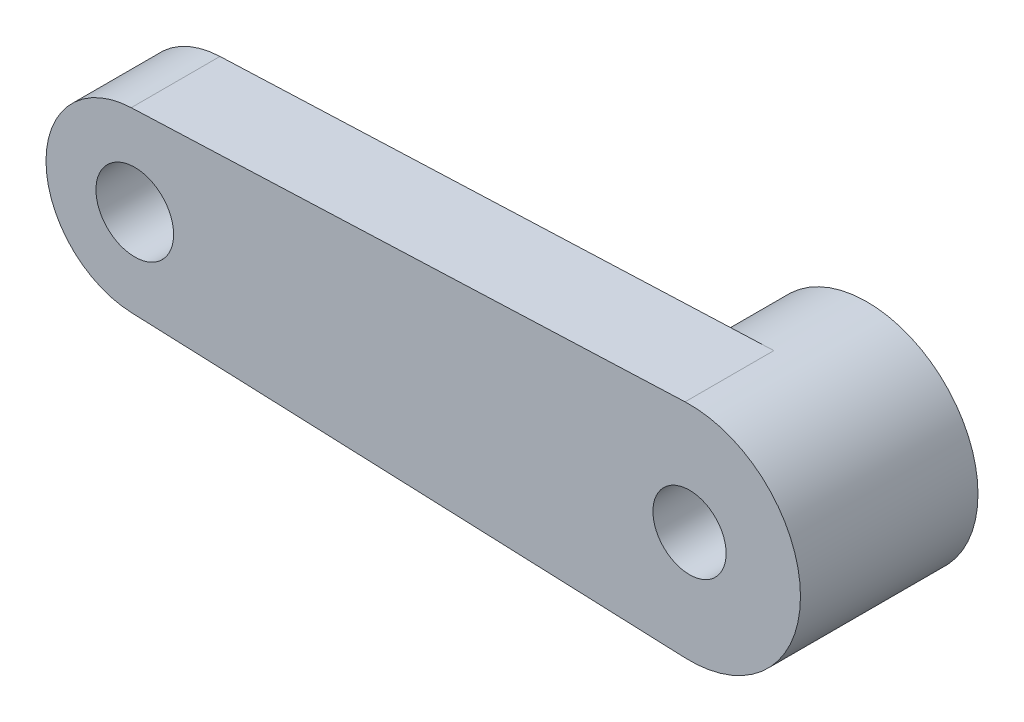
SolidWorks part; units mm, degrees
ref_plane "Front Plane" through (0, 0, 0) normal (0, 0, 1) x (1, 0, 0)
ref_plane "Top Plane" through (0, 0, 0) normal (0, 1, 0) x (1, 0, 0)
ref_plane "Right Plane" through (0, 0, 0) normal (1, 0, 0) x (0, 0, -1)
sketch "Sketch1" plane through (0, 0, 0) normal (0, 0, 1) x (1, 0, 0)
  line L96 (0.2308, 2.8251) -> (0.1696, 2.7453)
  line L97 (0.1696, 2.7453) -> (0.1212, 2.8292)
  line L98 (-0.1379, 2.8447) -> (-0.1902, 2.7542)
  line L99 (-0.1902, 2.7542) -> (-0.2514, 2.834)
  line L100 (-0.509, 2.8001) -> (-0.5474, 2.7072)
  line L101 (-0.5474, 2.7072) -> (-0.6186, 2.7783)
  line L102 (-0.8695, 2.7111) -> (-0.8955, 2.6139)
  line L103 (-0.8955, 2.6139) -> (-0.9753, 2.6752)
  line L104 (-1.2153, 2.5757) -> (-1.2285, 2.476)
  line L105 (-1.2285, 2.476) -> (-1.3156, 2.5263)
  line L106 (-1.5406, 2.3964) -> (-1.5406, 2.2958)
  line L107 (-1.5406, 2.2958) -> (-1.6335, 2.3343)
  line L108 (-1.8396, 2.1762) -> (-1.8265, 2.0765)
  line L109 (-1.8265, 2.0765) -> (-1.9236, 2.1025)
  line L110 (-2.1073, 1.9188) -> (-2.0813, 1.8216)
  line L111 (-2.0813, 1.8216) -> (-2.181, 1.8348)
  line L112 (-2.3391, 1.6287) -> (-2.3007, 1.5357)
  line L113 (-2.3007, 1.5357) -> (-2.4012, 1.5357)
  line L114 (-2.5311, 1.3107) -> (-2.4809, 1.2237)
  line L115 (-2.4809, 1.2237) -> (-2.5806, 1.2105)
  line L116 (-2.68, 0.9705) -> (-2.6188, 0.8907)
  line L117 (-2.6188, 0.8907) -> (-2.7159, 0.8647)
  line L118 (-2.7831, 0.6137) -> (-2.712, 0.5426)
  line L119 (-2.712, 0.5426) -> (-2.8049, 0.5041)
  line L120 (-2.8388, 0.2466) -> (-2.7591, 0.1853)
  line L121 (-2.7591, 0.1853) -> (-2.8462, 0.1351)
  line L122 (-2.8462, -0.1248) -> (-2.7591, -0.175)
  line L123 (-2.7591, -0.175) -> (-2.8388, -0.2363)
  line L124 (-2.8049, -0.4938) -> (-2.712, -0.5323)
  line L125 (-2.712, -0.5323) -> (-2.7831, -0.6034)
  line L126 (-2.7159, -0.8544) -> (-2.6188, -0.8804)
  line L127 (-2.6188, -0.8804) -> (-2.68, -0.9602)
  line L128 (-2.5806, -1.2002) -> (-2.4809, -1.2134)
  line L129 (-2.4809, -1.2134) -> (-2.5311, -1.3004)
  line L130 (-2.4012, -1.5254) -> (-2.3007, -1.5254)
  line L131 (-2.3007, -1.5254) -> (-2.3391, -1.6184)
  line L132 (-2.181, -1.8245) -> (-2.0813, -1.8113)
  line L133 (-2.0813, -1.8113) -> (-2.1073, -1.9085)
  line L134 (-1.9236, -2.0922) -> (-1.8265, -2.0662)
  line L135 (-1.8265, -2.0662) -> (-1.8396, -2.1659)
  line L136 (-1.6335, -2.324) -> (-1.5406, -2.2855)
  line L137 (-1.5406, -2.2855) -> (-1.5406, -2.3861)
  line L138 (-1.3156, -2.516) -> (-1.2285, -2.4657)
  line L139 (-1.2285, -2.4657) -> (-1.2153, -2.5654)
  line L140 (-0.9753, -2.6649) -> (-0.8955, -2.6036)
  line L141 (-0.8955, -2.6036) -> (-0.8695, -2.7008)
  line L142 (-0.6186, -2.768) -> (-0.5474, -2.6969)
  line L143 (-0.5474, -2.6969) -> (-0.509, -2.7898)
  line L144 (-0.2514, -2.8237) -> (-0.1902, -2.7439)
  line L145 (-0.1902, -2.7439) -> (-0.1399, -2.831)
  line L146 (0.1199, -2.831) -> (0.1702, -2.7439)
  line L147 (0.1702, -2.7439) -> (0.2314, -2.8237)
  line L148 (0.489, -2.7898) -> (0.5275, -2.6969)
  line L149 (0.5275, -2.6969) -> (0.5986, -2.768)
  line L150 (0.8496, -2.7008) -> (0.8756, -2.6036)
  line L151 (0.8756, -2.6036) -> (0.9554, -2.6649)
  line L152 (1.1954, -2.5654) -> (1.2085, -2.4657)
  line L153 (1.2085, -2.4657) -> (1.2956, -2.516)
  line L154 (1.5206, -2.3861) -> (1.5206, -2.2855)
  line L155 (1.5206, -2.2855) -> (1.6135, -2.324)
  line L156 (1.8197, -2.1659) -> (1.8065, -2.0662)
  line L157 (1.8065, -2.0662) -> (1.9037, -2.0922)
  line L158 (2.0874, -1.9085) -> (2.0613, -1.8113)
  line L159 (2.0613, -1.8113) -> (2.161, -1.8245)
  line L160 (2.3192, -1.6184) -> (2.2807, -1.5254)
  line L161 (2.2807, -1.5254) -> (2.3813, -1.5254)
  line L162 (2.5112, -1.3004) -> (2.4609, -1.2134)
  line L163 (2.4609, -1.2134) -> (2.5606, -1.2002)
  line L164 (2.66, -0.9602) -> (2.5988, -0.8804)
  line L165 (2.5988, -0.8804) -> (2.696, -0.8544)
  line L166 (2.7632, -0.6034) -> (2.6921, -0.5323)
  line L167 (2.6921, -0.5323) -> (2.785, -0.4938)
  line L168 (2.8189, -0.2363) -> (2.7391, -0.175)
  line L169 (2.7391, -0.175) -> (2.8315, -0.1217)
  line L170 (2.8304, 0.1234) -> (2.7385, 0.1764)
  line L171 (2.7385, 0.1764) -> (2.8183, 0.2376)
  line L172 (2.7844, 0.4952) -> (2.6915, 0.5337)
  line L173 (2.6915, 0.5337) -> (2.7626, 0.6048)
  line L174 (2.6953, 0.8557) -> (2.5982, 0.8818)
  line L175 (2.5982, 0.8818) -> (2.6594, 0.9615)
  line L176 (2.56, 1.2016) -> (2.4603, 1.2147)
  line L177 (2.4603, 1.2147) -> (2.5106, 1.3018)
  line L178 (2.3807, 1.5268) -> (2.2801, 1.5268)
  line L179 (2.2801, 1.5268) -> (2.3186, 1.6197)
  line L180 (2.1604, 1.8258) -> (2.0607, 1.8127)
  line L181 (2.0607, 1.8127) -> (2.0867, 1.9098)
  line L182 (1.903, 2.0935) -> (1.8059, 2.0675)
  line L183 (1.8059, 2.0675) -> (1.819, 2.1672)
  line L184 (1.6129, 2.3254) -> (1.52, 2.2869)
  line L185 (1.52, 2.2869) -> (1.52, 2.3875)
  line L186 (1.295, 2.5174) -> (1.2079, 2.4671)
  line L187 (1.2079, 2.4671) -> (1.1948, 2.5668)
  line L188 (0.9548, 2.6662) -> (0.875, 2.605)
  line L189 (0.875, 2.605) -> (0.8489, 2.7021)
  line L190 (0.598, 2.7694) -> (0.5269, 2.6983)
  line L191 (0.5269, 2.6983) -> (0.4884, 2.7912)
  arc A71 (0.1212, 2.8292) -> (-0.1379, 2.8447) centre (-0.0129, 2.7619) ccw
  arc A72 (-0.2514, 2.834) -> (-0.509, 2.8001) centre (-0.3704, 2.7427) ccw
  arc A73 (-0.6186, 2.7783) -> (-0.8695, 2.7111) centre (-0.7246, 2.6723) ccw
  arc A74 (-0.9753, 2.6752) -> (-1.2153, 2.5757) centre (-1.0666, 2.5562) ccw
  arc A75 (-1.3156, 2.5263) -> (-1.5406, 2.3964) centre (-1.3906, 2.3964) ccw
  arc A76 (-1.6335, 2.3343) -> (-1.8396, 2.1762) centre (-1.6909, 2.1957) ccw
  arc A77 (-1.9236, 2.1025) -> (-2.1073, 1.9188) centre (-1.9624, 1.9576) ccw
  arc A78 (-2.181, 1.8348) -> (-2.3391, 1.6287) centre (-2.2006, 1.6861) ccw
  arc A79 (-2.4012, 1.5357) -> (-2.5311, 1.3107) centre (-2.4012, 1.3857) ccw
  arc A80 (-2.5806, 1.2105) -> (-2.68, 0.9705) centre (-2.561, 1.0618) ccw
  arc A81 (-2.7159, 0.8647) -> (-2.7831, 0.6137) centre (-2.6771, 0.7198) ccw
  arc A82 (-2.8049, 0.5041) -> (-2.8388, 0.2466) centre (-2.7475, 0.3656) ccw
  arc A83 (-2.8462, 0.1351) -> (-2.8462, -0.1248) centre (-2.7712, 0.0051) ccw
  arc A84 (-2.8388, -0.2363) -> (-2.8049, -0.4938) centre (-2.7475, -0.3553) ccw
  arc A85 (-2.7831, -0.6034) -> (-2.7159, -0.8544) centre (-2.6771, -0.7095) ccw
  arc A86 (-2.68, -0.9602) -> (-2.5806, -1.2002) centre (-2.561, -1.0515) ccw
  arc A87 (-2.5311, -1.3004) -> (-2.4012, -1.5254) centre (-2.4012, -1.3754) ccw
  arc A88 (-2.3391, -1.6184) -> (-2.181, -1.8245) centre (-2.2006, -1.6758) ccw
  arc A89 (-2.1073, -1.9085) -> (-1.9236, -2.0922) centre (-1.9624, -1.9473) ccw
  arc A90 (-1.8396, -2.1659) -> (-1.6335, -2.324) centre (-1.6909, -2.1854) ccw
  arc A91 (-1.5406, -2.3861) -> (-1.3156, -2.516) centre (-1.3906, -2.3861) ccw
  arc A92 (-1.2153, -2.5654) -> (-0.9753, -2.6649) centre (-1.0666, -2.5459) ccw
  arc A93 (-0.8695, -2.7008) -> (-0.6186, -2.768) centre (-0.7246, -2.662) ccw
  arc A94 (-0.509, -2.7898) -> (-0.2514, -2.8237) centre (-0.3704, -2.7324) ccw
  arc A95 (-0.1399, -2.831) -> (0.1199, -2.831) centre (-0.01, -2.756) ccw
  arc A96 (0.2314, -2.8237) -> (0.489, -2.7898) centre (0.3504, -2.7324) ccw
  arc A97 (0.5986, -2.768) -> (0.8496, -2.7008) centre (0.7047, -2.662) ccw
  arc A98 (0.9554, -2.6649) -> (1.1954, -2.5654) centre (1.0467, -2.5459) ccw
  arc A99 (1.2956, -2.516) -> (1.5206, -2.3861) centre (1.3706, -2.3861) ccw
  arc A100 (1.6135, -2.324) -> (1.8197, -2.1659) centre (1.6709, -2.1854) ccw
  arc A101 (1.9037, -2.0922) -> (2.0874, -1.9085) centre (1.9425, -1.9473) ccw
  arc A102 (2.161, -1.8245) -> (2.3192, -1.6184) centre (2.1806, -1.6758) ccw
  arc A103 (2.3813, -1.5254) -> (2.5112, -1.3004) centre (2.3813, -1.3754) ccw
  arc A104 (2.5606, -1.2002) -> (2.66, -0.9602) centre (2.541, -1.0515) ccw
  arc A105 (2.696, -0.8544) -> (2.7632, -0.6034) centre (2.6571, -0.7095) ccw
  arc A106 (2.785, -0.4938) -> (2.8189, -0.2363) centre (2.7276, -0.3553) ccw
  arc A107 (2.8315, -0.1217) -> (2.8304, 0.1234) centre (2.7444, 0.0004) ccw
  arc A108 (2.8183, 0.2376) -> (2.7844, 0.4952) centre (2.727, 0.3566) ccw
  arc A109 (2.7626, 0.6048) -> (2.6953, 0.8557) centre (2.6565, 0.7108) ccw
  arc A110 (2.6594, 0.9615) -> (2.56, 1.2016) centre (2.5404, 1.0529) ccw
  arc A111 (2.5106, 1.3018) -> (2.3807, 1.5268) centre (2.3807, 1.3768) ccw
  arc A112 (2.3186, 1.6197) -> (2.1604, 1.8258) centre (2.18, 1.6771) ccw
  arc A113 (2.0867, 1.9098) -> (1.903, 2.0935) centre (1.9419, 1.9487) ccw
  arc A114 (1.819, 2.1672) -> (1.6129, 2.3254) centre (1.6703, 2.1868) ccw
  arc A115 (1.52, 2.3875) -> (1.295, 2.5174) centre (1.37, 2.3875) ccw
  arc A116 (1.1948, 2.5668) -> (0.9548, 2.6662) centre (1.0461, 2.5472) ccw
  arc A117 (0.8489, 2.7021) -> (0.598, 2.7694) centre (0.7041, 2.6633) ccw
  arc A118 (0.4884, 2.7912) -> (0.2308, 2.8251) centre (0.3498, 2.7338) ccw
  circle A119 centre (0, 0) radius 5
  dimension "D1" = 2.7453
  dimension "D2" = 10
extrude "Boss-Extrude1" add sketch "Sketch1" along normal blind 4
sketch "Sketch2" plane through (0, 0, 4) normal (0, 0, 1) x (1, 0, 0)
  line L0 (-25.16, 3.9968) -> (-0.2, 4.996)
  line L1 (-25.16, -3.9968) -> (-0.2, -4.996)
  circle A0 centre (0, 0) radius 1.65
  circle A2 centre (-25, 0) radius 1.75
  arc A3 (-25.16, 3.9968) -> (-25.16, -3.9968) centre (-25, 0) ccw
  circle A5 centre (0, 0) radius 5 construction
  arc A6 (-0.2, -4.996) -> (-0.2, 4.996) centre (0, 0) ccw
  dimension "D1" = 3.3
  dimension "D2" = 25
  dimension "D3" = 3.5
  dimension "D4" = 8
extrude "Boss-Extrude2" add sketch "Sketch2" along normal blind 4
